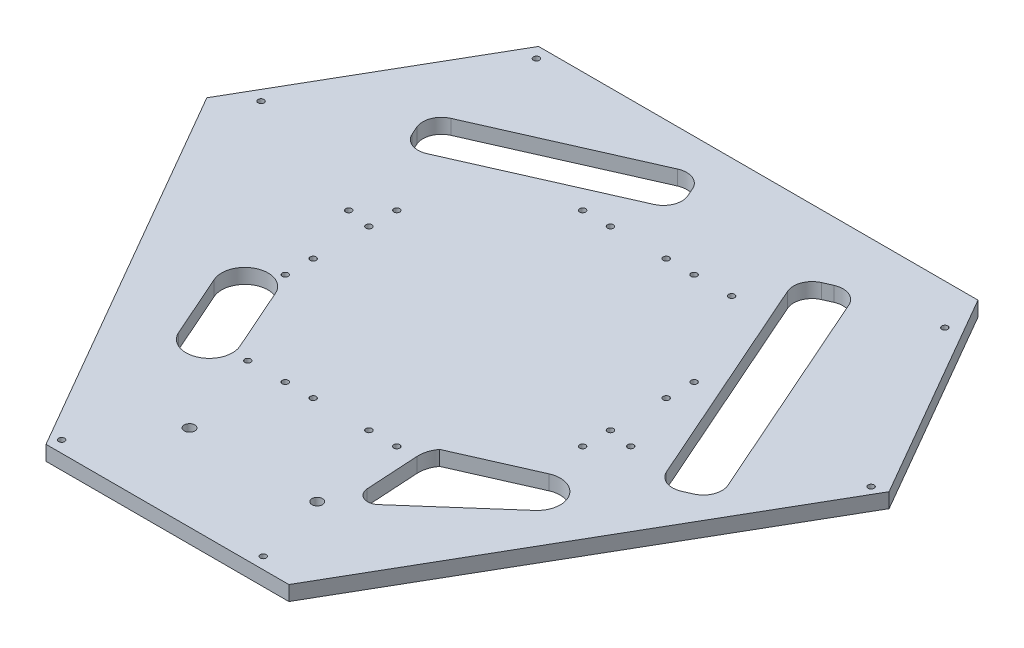
SolidWorks part; units mm, degrees
material "Pin"
ref_plane "Plan de face" through (0, 0, 0) normal (0, 0, 1) x (1, 0, 0)
ref_plane "Plan de dessus" through (0, 0, 0) normal (0, 1, 0) x (1, 0, 0)
ref_plane "Plan de droite" through (0, 0, 0) normal (1, 0, 0) x (0, 0, -1)
sketch "BB_position" plane through (0, 0, 0) normal (0, 1, 0) x (1, 0, 0)
  line L0 (-112.5, 64.9519) -> (112.5, 64.9519) construction
  line L7 (112.5, 64.9519) -> (0, -129.9038) construction
  line L8 (0, -129.9038) -> (-112.5, 64.9519) construction
  circle A0 centre (0, 0) radius 129.9038 construction
  circle A1 centre (-112.5, 64.9519) radius 5 construction
  circle A2 centre (112.5, 64.9519) radius 5 construction
  circle A3 centre (0, -129.9038) radius 5 construction
  dimension "D1" = 225
  dimension "D2" = 10
sketch "BB_Footprint" plane through (0, 0, 0) normal (0, 1, 0) x (1, 0, 0)
  line L0 (-112.5, 64.9519) -> (-130.615, 33.5758) construction
  line L1 (-130.615, 33.5758) -> (-133.9232, 35.4858) construction
  line L2 (-133.9232, 35.4858) -> (-90.5354, 110.6358) construction
  line L3 (97.6932, 98.238) -> (141.0811, 23.088) construction
  line L4 (112.5, 64.9519) -> (94.385, 96.328) construction
  line L5 (94.385, 96.328) -> (97.6932, 98.238) construction
  line L6 (36.23, -133.7238) -> (-50.5457, -133.7238) construction
  line L7 (0, -129.9038) -> (36.23, -129.9038) construction
  line L8 (36.23, -129.9038) -> (36.23, -133.7238) construction
  circle A0 centre (-112.5, 64.9519) radius 5 construction
  circle A1 centre (0, 0) radius 129.9038 construction
  circle A2 centre (-112.5, 64.9519) radius 5 construction
  circle A3 centre (112.5, 64.9519) radius 5 construction
  circle A4 centre (0, -129.9038) radius 5 construction
  point P23 (0, 0)
  dimension "D1" = 3.82
  dimension "D2" = 36.23
  dimension "D3" = 86.7757
  dimension "D4" = 3
sketch "Esquisse3" plane through (0, 0, 0) normal (0, 1, 0) x (1, 0, 0)
  line L0 (-94.5768, 115.6358) -> (94.5768, 115.6358)
  line L1 (-94.5768, 115.6358) -> (-146.8546, 25.088)
  line L2 (-146.8546, 25.088) -> (-52.2778, -138.7238)
  line L3 (-52.2778, -138.7238) -> (52.2778, -138.7238)
  line L4 (52.2778, -138.7238) -> (146.8546, 25.088)
  line L5 (146.8546, 25.088) -> (94.5768, 115.6358)
  line L6 (-133.9232, 35.4858) -> (-90.5354, 110.6358) construction
  point P2 (0, 115.6358)
  point P7 (0, -138.7238)
  dimension "D1" = 5
  dimension "D2" = 4
  dimension "D3" = 5
sketch "TB_boltPattern" plane through (0, 0, 0) normal (0, 1, 0) x (1, 0, 0)
  line L0 (0, 143.3581) -> (0, -141.7362) construction
  line L1 (-23, 57.7) -> (-13, 57.7) construction
  line L2 (-23, 57.7) -> (-23, 43.7) construction
  line L3 (-23, 43.7) -> (-13, 43.7) construction
  line L4 (-13, 57.7) -> (-13, 43.7) construction
  line L5 (-57.7, 23) -> (-43.7, 23) construction
  line L6 (-57.7, 23) -> (-57.7, 13) construction
  line L7 (-57.7, 13) -> (-43.7, 13) construction
  line L8 (-43.7, 23) -> (-43.7, 13) construction
  line L9 (-204.4729, 0) -> (279.6048, 0) construction
  circle A0 centre (-24, 64) radius 1.6 construction
  circle A1 centre (-12, 64) radius 1.6 construction
  circle A2 centre (-64, 24) radius 1.6 construction
  circle A3 centre (-64, 12) radius 1.6 construction
  point P8 (-18, 57.7)
  dimension "D5" = 3.2
  dimension "D10" = 6.3
  dimension "D1" = 12
  dimension "D2" = 12
  dimension "D3" = 40
  dimension "D4" = 40
  dimension "D6" = 14
  dimension "D7" = 10
  dimension "D8" = 1
  dimension "D9" = 6.3
  dimension "D11" = 1
  dimension "D12" = 12
  dimension "D13" = 12
extrude "Plate" add sketch "Esquisse3" against normal blind 6.35
hole_wizard "BBCase_boltPattern" positions "Esquisse6" profile "Esquisse8" hole size "M3" standard "Ansi Metric"
sketch "Esquisse6" plane through (0, 0, 0) normal (0, 1, 0) x (1, 0, 0)
  point P0 (-90.5354, 110.6358)
  point P3 (-133.9232, 35.4858)
sketch "Esquisse8" plane through (-90.5354, 0, -110.6358) normal (1, 0, 0) x (0, 0, 1)
  line L0 (0, 0) -> (0, 7.1311)
  line L1 (0, 7.1311) -> (1.3, 6.35)
  line L2 (1.3, 6.35) -> (1.3, 0)
  line L5 (1.3, 0) -> (0, 0)
  line L10 (0, 7.1311) -> (-1.3, 6.35) construction
  line L11 (0, -6.35) -> (0, 107.95) construction
  dimension "Diamètre du perçage" = 2.6
  dimension "Profondeur du perçage" = 6.35
  dimension "Angle de pointe" = 118
ref_axis "Axe1" through (0, 0, 0) along (0, 1, 0)
pattern_circular "Répétition circulaire1" count 3 over 360 about axis through (0, 0, 0) along (0, 1, 0) of "BBCase_boltPattern"
hole_wizard "Dégagement M32" positions "Esquisse9" profile "Esquisse10" hole size "M3" standard "Ansi Metric"
sketch "Esquisse9" plane through (0, 0, 0) normal (0, 1, 0) x (1, 0, 0)
  point P0 (-24, 64)
  point P3 (-12, 64)
  point P6 (-64, 24)
  point P9 (-64, 12)
sketch "Esquisse10" plane through (-24, 0, -64) normal (1, 0, 0) x (0, 0, 1)
  line L0 (0, 0) -> (0, 7.1311)
  line L1 (0, 7.1311) -> (1.3, 6.35)
  line L2 (1.3, 6.35) -> (1.3, 0)
  line L5 (1.3, 0) -> (0, 0)
  line L10 (0, 7.1311) -> (-1.3, 6.35) construction
  line L11 (0, -6.35) -> (0, 107.95) construction
  dimension "Diamètre du perçage" = 2.6
  dimension "Profondeur du perçage" = 6.35
  dimension "Angle de pointe" = 118
pattern_circular "Répétition circulaire2" count 4 over 360 about axis through (0, 0, 0) along (0, 1, 0) of "Dégagement M32"
sketch "HB_Footprint" plane through (0, 0, 0) normal (0, 1, 0) x (1, 0, 0)
  line L0 (-74.3426, 13.6262) -> (40.0015, 64.1278) construction
  line L1 (40.0015, 64.1278) -> (74.3426, -13.6262) construction
  line L2 (-74.3426, 13.6262) -> (-40.0015, -64.1278) construction
  line L3 (-40.0015, -64.1278) -> (74.3426, -13.6262) construction
  line L8 (-77.8072, 30.1336) -> (-30.1336, -77.8072) construction
  line L9 (-30.1336, -77.8072) -> (77.8072, -30.1336) construction
  line L10 (77.8072, -30.1336) -> (30.1336, 77.8072) construction
  line L11 (-77.8072, 30.1336) -> (30.1336, 77.8072) construction
  line L12 (-23.8368, 53.9704) -> (23.8368, -53.9704) construction
  line L13 (-57.1721, -25.2508) -> (0, 0) construction
  circle A0 centre (-74.3426, 13.6262) radius 1.6 construction
  circle A1 centre (40.0015, 64.1278) radius 1.6 construction
  circle A2 centre (-40.0015, -64.1278) radius 1.6 construction
  circle A3 centre (74.3426, -13.6262) radius 1.6 construction
  point P10 (23.8368, -53.9704)
  point P19 (-17.1706, 38.877)
  dimension "D4" = 3.2
  dimension "D1" = 125
  dimension "D2" = 85
  dimension "D3" = 118
hole_wizard "Dégagement M33" positions "Esquisse11" profile "Esquisse12" hole size "M3" standard "Ansi Metric"
sketch "Esquisse11" plane through (0, 0, 0) normal (0, 1, 0) x (1, 0, 0)
  point P0 (-74.3426, 13.6262)
  point P3 (-40.0015, -64.1278)
  point P6 (74.3426, -13.6262)
  point P9 (40.0015, 64.1278)
sketch "Esquisse12" plane through (-74.3426, 0, -13.6262) normal (1, 0, 0) x (0, 0, 1)
  line L0 (0, 0) -> (0, 7.1311)
  line L1 (0, 7.1311) -> (1.3, 6.35)
  line L2 (1.3, 6.35) -> (1.3, 0)
  line L5 (1.3, 0) -> (0, 0)
  line L10 (0, 7.1311) -> (-1.3, 6.35) construction
  line L11 (0, -6.35) -> (0, 107.95) construction
  dimension "Diamètre du perçage" = 2.6
  dimension "Profondeur du perçage" = 6.35
  dimension "Angle de pointe" = 118
sketch "Esquisse13" plane through (0, 0, 0) normal (0, 1, 0) x (1, 0, 0)
  line L0 (113.0252, -14.5791) -> (94.7302, -22.6594)
  line L1 (94.7302, -22.6594) -> (47.0566, 85.2815)
  line L2 (47.0566, 85.2815) -> (65.3516, 93.3617)
  line L3 (65.3516, 93.3617) -> (113.0252, -14.5791)
  line L5 (-77.8072, 30.1336) -> (30.1336, 77.8072) construction
  line L7 (40.0015, 64.1278) -> (74.3426, -13.6262) construction
  line L13 (-30.1336, -77.8072) -> (77.8072, -30.1336) construction
  line L14 (-11.64, 103.085) -> (-93.9678, 66.7238)
  line L15 (-93.9678, 66.7238) -> (-85.8875, 48.4287)
  line L16 (-85.8875, 48.4287) -> (-3.5597, 84.7899)
  line L17 (-3.5597, 84.7899) -> (-11.64, 103.085)
  line L18 (-77.8072, 30.1336) -> (-30.1336, -77.8072) construction
  dimension "D1" = 15
  dimension "D2" = 20
  dimension "D5" = 20
  dimension "D6" = 90
  dimension "D7" = 20
extrude "Enlèv. mat.-Extru.1" cut sketch "Esquisse13" against normal up to surface (6.35 mm away) up to face at (-40.0015, -6.35, 65.4278)
sketch "Esquisse15" plane through (0, 0, 0) normal (0, 1, 0) x (1, 0, 0)
  line L0 (-27.48, -101.7238) -> (27.48, -101.7238) construction
  line L1 (0, 200143.3581) -> (0, -200141.7362) construction
  line L2 (-52.2778, -138.7238) -> (52.2778, -138.7238) construction
  circle A0 centre (-27.48, -101.7238) radius 3.5746 construction
  circle A1 centre (27.48, -101.7238) radius 3.5746 construction
  point P4 (0, -101.7238)
  dimension "D1" = 54.96
  dimension "D2" = 37
hole_wizard "Dégagement M51" positions "Esquisse16" profile "Esquisse17" hole size "M5" standard "Ansi Metric"
sketch "Esquisse16" plane through (0, 0, 0) normal (0, 1, 0) x (1, 0, 0)
  point P0 (-27.48, -101.7238)
  point P3 (27.48, -101.7238)
sketch "Esquisse17" plane through (-27.48, 0, 101.7238) normal (1, 0, 0) x (0, 0, 1)
  line L0 (0, 0) -> (0, 7.714)
  line L1 (0, 7.714) -> (2.27, 6.35)
  line L2 (2.27, 6.35) -> (2.27, 0)
  line L5 (2.27, 0) -> (0, 0)
  line L10 (0, 7.714) -> (-2.27, 6.35) construction
  line L11 (0, -6.35) -> (0, 107.95) construction
  dimension "Diamètre du perçage" = 4.54
  dimension "Profondeur du perçage" = 6.35
  dimension "Angle de pointe" = 118
sketch "Esquisse18" plane through (0, 0, 0) normal (0, 1, 0) x (1, 0, 0)
  line L0 (71.0075, -50.6279) -> (43.5649, -62.7483) construction
  line L2 (66.9674, -41.4803) -> (34.336, -55.8925)
  line L3 (-30.1336, -77.8072) -> (77.8072, -30.1336) construction
  line L4 (23.8368, -53.9704) -> (77.8072, -30.1336) construction
  line L5 (50.822, -42.052) -> (57.2862, -56.6881) construction
  line L6 (-68.3683, -37.0282) -> (-56.2479, -64.4708) construction
  line L7 (-59.2207, -32.9881) -> (-47.1003, -60.4307)
  line L8 (-77.5158, -41.0684) -> (-65.3954, -68.511)
  line L9 (-74.3426, 13.6262) -> (-40.0015, -64.1278) construction
  line L10 (-57.1721, -25.2508) -> (-40.0015, -64.1278) construction
  line L11 (-48.5868, -44.6893) -> (-62.3081, -50.7495) construction
  line L12 (32.0883, -63.4284) -> (33.4385, -86.2128)
  line L13 (41.7305, -89.6726) -> (77.6091, -58.1391)
  arc A0 (77.6091, -58.1391) -> (66.9674, -41.4803) centre (71.0075, -50.6279) ccw
  arc A1 (34.336, -55.8925) -> (32.0883, -63.4284) centre (43.5649, -62.7483) ccw
  arc A2 (-59.2207, -32.9881) -> (-77.5158, -41.0684) centre (-68.3683, -37.0282) ccw
  arc A3 (-65.3954, -68.511) -> (-47.1003, -60.4307) centre (-56.2479, -64.4708) ccw
  arc A4 (33.4385, -86.2128) -> (41.7305, -89.6726) centre (38.4297, -85.917) ccw
  point P2 (57.2862, -56.6881)
  point P16 (-62.3081, -50.7495)
  point P35 (34.0438, -96.4284)
  dimension "D4" = 15
  dimension "D6" = 10
  dimension "D1" = 10
  dimension "D11" = 5
  dimension "D2" = 6
  dimension "D3" = 30
  dimension "D5" = 30
  dimension "D7" = 35
  dimension "D8" = 58
  dimension "D9" = 10
  dimension "D10" = 33
extrude "Enlèv. mat.-Extru.3" cut sketch "Esquisse18" against normal up to surface (6.35 mm away) up to face at (-27.48, -6.35, 103.9938)
fillet "Congé1" radius 8 8 edges at (47.0566, -3.175, -85.2815) (65.3516, -3.175, -93.3617) (113.0252, -3.175, 14.5791) (94.7302, -3.175, 22.6594) (-11.64, -3.175, -103.085) (-3.5597, -3.175, -84.7899) (-85.8875, -3.175, -48.4287) (-93.9678, -3.175, -66.7238)
